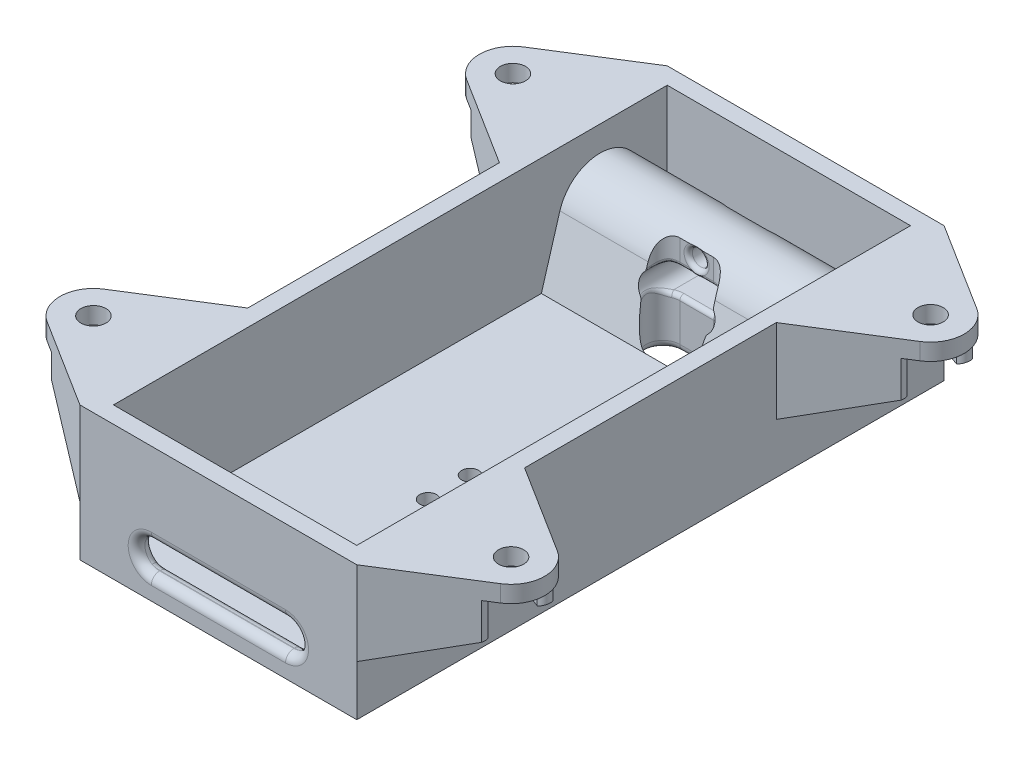
SolidWorks part; units mm, degrees
material "ABS"
ref_plane "Front Plane" through (0, 0, 0) normal (0, 0, 1) x (1, 0, 0)
ref_plane "Top Plane" through (0, 0, 0) normal (0, 1, 0) x (1, 0, 0)
ref_plane "Right Plane" through (0, 0, 0) normal (1, 0, 0) x (0, 0, -1)
sketch "Sketch1" plane through (0, 0, 0) normal (0, 1, 0) x (1, 0, 0)
  line L1 (16.5, -35) -> (-16.5, -35)
  line L2 (16.5, -35) -> (16.5, 35)
  line L3 (16.5, 35) -> (-16.5, 35)
  line L4 (-16.5, -35) -> (-16.5, 35)
  line L5 (16.5, -35) -> (-16.5, 35) construction
  line L6 (16.5, 35) -> (-16.5, -35) construction
  point P0 (0, 0)
  dimension "D1" = 70
  dimension "D2" = 33
extrude "Boss-Extrude1" add sketch "Sketch1" along normal blind 2
sketch "Sketch2" plane through (0, 2, 0) normal (0, 1, 0) x (1, 0, 0)
  line L1 (16.5, 35) -> (-16.5, 35) construction
  circle A0 centre (0, -10) radius 1
  circle A1 centre (0, -5) radius 1
  dimension "D1" = 5
  dimension "D2" = 45
extrude "Cut-Extrude1" cut sketch "Sketch2" against normal blind 2
sketch "Sketch3" plane through (0, 2, 0) normal (0, 1, 0) x (1, 0, 0)
  line L0 (2, 30) -> (-2, 30) construction
  line L1 (0, 14.1108) -> (0, 50014.1108) construction
  line L4 (2, 20) -> (-2, 20) construction
  line L5 (16.5, 35) -> (-16.5, 35) construction
  line L6 (2, 18) -> (-2, 18)
  line L7 (2, 28) -> (-2, 28)
  line L8 (2, 32) -> (-2, 32)
  line L9 (2, 22) -> (-2, 22)
  arc A0 (2, 28) -> (2, 32) centre (2, 30) ccw
  arc A1 (-2, 32) -> (-2, 28) centre (-2, 30) ccw
  arc A4 (2, 18) -> (2, 22) centre (2, 20) ccw
  arc A5 (-2, 22) -> (-2, 18) centre (-2, 20) ccw
  point P0 (0, 14.1108)
  point P4 (0, 20)
  point P7 (0, 30)
  point P19 (0, 20)
  dimension "D1" = 5
  dimension "D3" = 2
  dimension "D5" = 2
  dimension "D2" = 4
  dimension "D4" = 4
  dimension "D6" = 15
  dimension "D7" = 0
  dimension "D8" = 0
sketch "Sketch6" plane through (0, 0, 0) normal (0, 0, 1) x (1, 0, 0)
  line L0 (0, -1000) -> (0, 49000) construction
  line L2 (3, 7.5) -> (-3, 7.5) construction
  line L3 (3, 6) -> (-3, 6)
  line L4 (3, 9) -> (-3, 9)
  circle A0 centre (0, 10.75) radius 1
  arc A1 (3, 6) -> (3, 9) centre (3, 7.5) ccw
  arc A2 (-3, 9) -> (-3, 6) centre (-3, 7.5) ccw
  point P9 (0, 7.5)
  dimension "D1" = 3.25
  dimension "D2" = 6
sketch "Sketch7" plane through (0, 2, 0) normal (0, 1, 0) x (1, 0, 0)
  line L1 (-16.5, 35) -> (16.5, 35)
  line L2 (-16.5, 35) -> (-16.5, -35)
  line L3 (-16.5, -35) -> (16.5, -35)
  line L4 (16.5, 35) -> (16.5, -35)
  line L5 (-14.5, 33) -> (14.5, 33)
  line L6 (-14.5, 33) -> (-14.5, -33)
  line L7 (-14.5, -33) -> (14.5, -33)
  line L8 (14.5, 33) -> (14.5, -33)
  dimension "D1" = 2
  dimension "D2" = 2
  dimension "D3" = 2
  dimension "D4" = 2
extrude "Boss-Extrude3" add sketch "Sketch7" along normal blind 14
sketch "Sketch8" plane through (0, 0, 0) normal (1, 0, 0) x (0, 0, -1)
  line L0 (18.0007, 2) -> (32, 2)
  line L3 (32, 2) -> (28, 2) construction
  line L4 (32, 2) -> (28, 2) construction
  line L5 (25, 2) -> (25, 50002) construction
  line L6 (18.0007, 2) -> (20.2071, 9.4244)
  line L7 (32, 2) -> (29.7928, 9.4248)
  circle A0 centre (25, 8) radius 5.0001
extrude "Boss-Extrude5" add sketch "Sketch8" along normal up to surface and the other way up to surface contours A0 | A0 L6 L0 L7 | L0 L5 A0 L6 | L5 A0 region at (0, 3.7006, -20.8186) region at (0, 3.7008, -29.1817) region at (0, 8, -22.8779) region at (0, 8, -27.1221) up to face at (14.5, 9, 0) other way up to face at (-14.5, 9, 0)
extrude "Cut-Extrude2" cut sketch "Sketch3" against normal through all both and the other way through all
extrude "Cut-Extrude3" cut sketch "Sketch6" against normal up to surface (33 mm away) up to face at (0, 9, -33)
fillet "Fillet2" radius 1 8 edges at (4, 0, -30) (0, 0, -28) (-4, 0, -30) (4, 0, -20) (0, 0, -18) (-4, 0, -20) (0, 0, -32) (0, 0, -22)
fillet "Fillet3" radius 0.5 2 edges at (1, 10.75, -28) (-1, 10.75, -22)
fillet "Fillet4" radius 0.5 20 edges at (3.7216, 8.815, -28.982) (2.5176, 9, -28.0681) (-3.5444, 8.8977, -28.7293) (-2.5176, 9, -28.0681) (-3.7383, 8.8057, -20.9891) (-2.5176, 9, -21.9319) (3.7756, 8.7839, -20.9204) (2.5176, 9, -21.9319) (0, 9, -28) (0, 9, -22) (-3.9545, 6.3429, -29.5759) (-2.5176, 6, -28.0681) (3.8842, 6.2883, -29.3295) (2.5176, 6, -28.0681) (3.9545, 6.3429, -20.4241) (2.5176, 6, -21.9319) (-3.76, 6.2068, -20.9499) (-2.5176, 6, -21.9319) (0, 6, -28) (0, 6, -22)
sketch "Sketch9" plane through (0, 0, 0) normal (0, 1, 0) x (1, 0, 0)
  line L0 (0, 0) -> (-50000, 0) construction
  line L1 (0, 0) -> (0, 50000) construction
  line L2 (-48.8173, 25) -> (-32.3978, 25) construction
  line L3 (-64.689, -25) -> (49935.311, -25) construction
  line L4 (-16.5, 35) -> (-27.0181, 28.3839)
  line L5 (-27.0181, 21.6161) -> (-16.4995, 14.9997)
  line L6 (-28.8873, 25) -> (49951.1827, 25) construction
  line L7 (-16.5, 35) -> (-16.4995, 14.9997)
  line L8 (-16.4995, -966.2511) -> (-16.4995, 49033.7489) construction
  line L9 (16.5, -969.4916) -> (16.5, 49030.5084) construction
  line L10 (16.5, 35) -> (16.4995, 14.9997)
  line L11 (27.0181, 21.6161) -> (16.4995, 14.9997)
  line L12 (16.5, 35) -> (27.0181, 28.3839)
  line L13 (16.5, -35) -> (27.0181, -28.3839)
  line L14 (27.0181, -21.6161) -> (16.4995, -14.9997)
  line L15 (16.5, -35) -> (16.4995, -14.9997)
  line L16 (-16.5, -35) -> (-16.4995, -14.9997)
  line L17 (-27.0181, -21.6161) -> (-16.4995, -14.9997)
  line L18 (-16.5, -35) -> (-27.0181, -28.3839)
  circle A0 centre (-24.8896, 25) radius 1.5
  circle A1 centre (-24.8896, 25) radius 3.9977
  circle A2 centre (24.8896, 25) radius 3.9977
  circle A3 centre (24.8896, 25) radius 1.5
  circle A4 centre (24.8896, -25) radius 1.5
  circle A5 centre (24.8896, -25) radius 3.9977
  circle A6 centre (-24.8896, -25) radius 3.9977
  circle A7 centre (-24.8896, -25) radius 1.5
  dimension "D1" = 25
  dimension "D2" = 25
extrude "Boss-Extrude6" add sketch "Sketch9" along normal blind 10 from offset 6 contours A1 A0 | A1 L5 L7 L4 | L11 A2 L12 L10 | A2 A3 | L17 A6 L18 L16 | A6 A7 | A5 L14 L15 L13 | A5 A4 region at (-19.4936, 0, -24.9998) region at (-23.0114, 0, -28.4003) region at (19.4936, 0, -24.9998) region at (28.29, 0, -26.8782) region at (19.4936, 0, 24.9998) region at (21.005, 0, 25) region at (-19.4936, 0, 24.9998) region at (-28.7742, 0, 25)
sketch "Sketch10" plane through (0, 0, 0) normal (0, 0, 1) x (1, 0, 0)
  line L0 (-16.5, 6) -> (-28.8873, 6)
  line L1 (-28.8873, 6) -> (-28.8873, 13)
  line L3 (-28.8873, 16) -> (-28.8873, 6) construction
  line L4 (0, 0) -> (0, 50000) construction
  line L5 (28.8873, 11) -> (16.5, 6)
  line L6 (28.8873, 6) -> (28.8873, 11)
  line L7 (16.5, 6) -> (28.8873, 6)
  line L8 (-28.8873, 13) -> (-16.5, 6)
extrude "Cut-Extrude4" cut sketch "Sketch10" against normal through all both and the other way through all contours L0 | L5 L7 L6 region at (-24.7582, 8.3333, 0) region at (24.7582, 7.6667, 0)
sketch "Sketch11" plane through (0, 0, 0) normal (0, 1, 0) x (1, 0, 0)
  line L0 (0, -1000) -> (0, 49000) construction
  line L1 (-24.884, -975.0051) -> (-24.884, 20.272) construction
  line L2 (-29.7901, 24.9949) -> (48975.116, 24.9949) construction
  line L3 (24.884, 21.8763) -> (24.884, 28.0809) construction
  line L4 (17.9293, 32.4554) -> (17.9293, 17.4554)
  line L5 (-24.884, 28.0809) -> (-17.9293, 32.4554)
  line L6 (17.9293, 17.4554) -> (24.884, 21.8763)
  line L7 (-24.884, 21.8763) -> (-24.884, 28.0809) construction
  line L8 (24.884, 28.0809) -> (17.9293, 32.4554)
  line L9 (-17.9293, 17.4554) -> (-24.884, 21.8763)
  line L10 (-24.884, 29.7237) -> (-24.884, 49024.9949) construction
  line L11 (-1000, 0) -> (49000, 0) construction
  line L12 (-24.884, -21.8763) -> (-24.884, -28.0809) construction
  line L13 (24.884, -21.8763) -> (24.884, -28.0809) construction
  line L14 (-17.9293, -32.4554) -> (-17.9293, -17.4554)
  line L15 (-17.9293, -17.4554) -> (-24.884, -21.8763)
  line L16 (24.884, -28.0809) -> (17.9293, -32.4554)
  line L17 (17.9293, -17.4554) -> (24.884, -21.8763)
  line L18 (-24.884, -28.0809) -> (-17.9293, -32.4554)
  line L19 (17.9293, -32.4554) -> (17.9293, -17.4554)
  line L20 (-17.9293, 32.4554) -> (-17.9293, 17.4554)
  arc A0 (-25.6243, 29.2578) -> (-24.884, 28.0809) centre (-24.8838, 28.9023) ccw
  arc A1 (-24.884, 21.8763) -> (-25.6064, 20.7263) centre (-24.8836, 21.0741) ccw
  arc A2 (-25.6243, 29.2578) -> (-25.6064, 20.7263) centre (-24.6547, 24.9941) ccw
  circle A3 centre (24.884, 24.9949) radius 1.49
  arc A4 (25.6243, 29.2578) -> (25.6064, 20.7263) centre (24.6547, 24.9941) cw
  arc A5 (24.884, 21.8763) -> (25.6064, 20.7263) centre (24.8836, 21.0741) cw
  arc A6 (25.6243, 29.2578) -> (24.884, 28.0809) centre (24.8838, 28.9023) cw
  circle A7 centre (-24.884, -24.9949) radius 1.49
  arc A8 (25.6243, -29.2578) -> (24.884, -28.0809) centre (24.8838, -28.9023) ccw
  arc A9 (24.884, -21.8763) -> (25.6064, -20.7263) centre (24.8836, -21.0741) ccw
  arc A10 (25.6243, -29.2578) -> (25.6064, -20.7263) centre (24.6547, -24.9941) ccw
  circle A11 centre (24.884, -24.9949) radius 1.49
  arc A12 (-25.6243, -29.2578) -> (-25.6064, -20.7263) centre (-24.6547, -24.9941) cw
  arc A13 (-24.884, -21.8763) -> (-25.6064, -20.7263) centre (-24.8836, -21.0741) cw
  arc A14 (-25.6243, -29.2578) -> (-24.884, -28.0809) centre (-24.8838, -28.9023) cw
  circle A19 centre (-24.884, 24.9949) radius 1.49
extrude "Cut-Extrude6" cut sketch "Sketch11" along normal blind 14 contours L20 A19 | A12 A14 L18 L14 L15 A13 A7 | A8 A10 A9 L17 L19 L16 A11 | A4 A6 L8 L4 L6 A5 A3 region at (22.2703, 0, -24.9698) region at (-22.2703, 0, -24.9698) region at (-22.2703, 0, 24.9698) region at (22.2703, 0, 24.9698)
sketch "Sketch12" plane through (0, 0, 35) normal (0, 0, 1) x (1, 0, 0)
  line L0 (16.5, 11) -> (-49983.5, 11) construction
  line L1 (16.5, 16) -> (16.5, 6) construction
  line L2 (-16.5, 16) -> (-16.5, 6) construction
  line L3 (0, 0) -> (0, 50000) construction
  line L6 (-1000, 7.6836) -> (49000, 7.6836) construction
  line L7 (8, 6.1173) -> (-8, 6.1173)
  line L8 (-8, 2.6173) -> (8, 2.6173)
  arc A2 (8, 6.1173) -> (8, 2.6173) centre (8, 4.3673) cw
  arc A3 (-8, 2.6173) -> (-8, 6.1173) centre (-8, 4.3673) cw
  point P4 (16.5, 11)
  point P7 (-16.5, 11)
extrude "Cut-Extrude7" cut sketch "Sketch12" against normal up to next
fillet "Fillet5" radius 1 7 edges at (9.75, 4.3673, 33) (-9.75, 4.3673, 33) (9.75, 4.3673, 35) (0, 2.6173, 35) (-9.75, 4.3673, 35) (0, 6.1173, 33) (0, 6.1173, 35)
